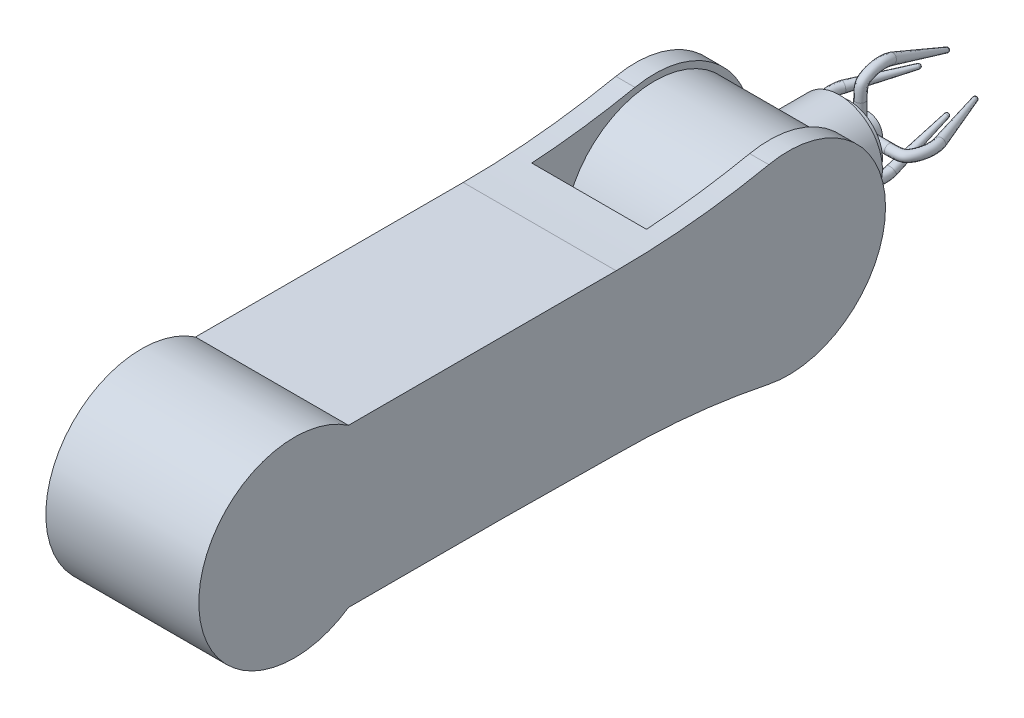
SolidWorks part; units mm, degrees
ref_plane "Front Plane" through (0, 0, 0) normal (0, 0, 1) x (1, 0, 0)
ref_plane "Top Plane" through (0, 0, 0) normal (0, 1, 0) x (1, 0, 0)
ref_plane "Right Plane" through (0, 0, 0) normal (1, 0, 0) x (0, 0, -1)
sketch "Sketch1" plane through (0, 0, 0) normal (1, 0, 0) x (0, 0, -1)
  circle A0 centre (0, 0) radius 50
  dimension "D1" = 100
extrude "Boss-Extrude1" add sketch "Sketch1" along normal mid plane 80
sketch "Sketch2" plane through (40, 0, 0) normal (1, 0, 0) x (0, 0, -1)
  line L0 (28.2566, 41.25) -> (28.2566, -41.25)
  line L1 (28.2566, -41.25) -> (108.2566, -41.25)
  line L2 (108.2566, -41.25) -> (108.2566, 41.25)
  line L3 (108.2566, 41.25) -> (28.2566, 41.25)
  circle A0 centre (0, 0) radius 50 construction
  dimension "D1" = 82.5
  dimension "D2" = 80
extrude "Boss-Extrude2" add sketch "Sketch2" against normal blind 80
ref_axis "Axis1" through (134.8481, 0, 0) along (-1, 0, 0)
sketch "Sketch5" plane through (0, 0, 0) normal (1, 0, 0) x (0, 0, -1)
  line L0 (108.2566, 41.25) -> (168.2566, 41.25)
  line L1 (168.2566, -41.9043) -> (108.2566, -41.25)
  line L2 (108.2566, -41.25) -> (108.2566, 41.25)
  line L3 (258.335, -0.3271) -> (393.5129, -0.3271) construction
  arc A0 (168.2566, 41.25) -> (248.0774, 49.3973) centre (168.2566, 436.3342) ccw
  arc A1 (248.0774, 49.3973) -> (248.0774, -50.0516) centre (258.335, -0.3271) cw
  arc A2 (248.0774, -50.0516) -> (168.2566, -41.9043) centre (168.2566, -436.9884) ccw
  dimension "D3" = 150.0784
  dimension "D1" = 60
  dimension "D2" = 60
extrude "Boss-Extrude4" add sketch "Sketch5" against normal mid plane 80
sketch "Sketch6" plane through (0, 0, 0) normal (0, 1, 0) x (1, 0, 0)
  line L0 (30, 260.643) -> (30, 309.1065)
  line L2 (40, 309.1065) -> (-40, 309.1065) construction
  line L3 (30, 309.1065) -> (-30, 309.1065)
  line L4 (-30, 309.1065) -> (-30, 260.643)
  line L6 (40, 168.2566) -> (40, 248.0774) construction
  line L7 (-40, 248.0774) -> (-40, 168.2566) construction
  line L9 (-30, 260.643) -> (-30, 217.1791)
  line L11 (30, 217.1791) -> (30, 260.643)
  line L12 (-30, 217.1791) -> (-30, 194.1065)
  line L13 (-30, 194.1065) -> (30, 194.1065)
  line L14 (30, 194.1065) -> (30, 217.1791)
  point P6 (0, 194.1065)
  dimension "D1" = 10
  dimension "D2" = 10
  dimension "D3" = 115
extrude "Cut-Extrude1" cut sketch "Sketch6" against normal mid plane 120
sketch "Sketch9" plane through (30, 0, 0) normal (-1, 0, 0) x (0, 0, 1)
  circle A0 centre (-258.335, -0.3271) radius 47.5
  dimension "D1" = 95
extrude "Boss-Extrude5" add sketch "Sketch9" along normal blind 60
ref_plane "Plane1" through (0, 0, -260) normal (0, 0, 1) x (1, 0, 0)
sketch "Sketch10" plane through (0, 0, -260) normal (0, 0, 1) x (1, 0, 0)
  circle A0 centre (0, 0) radius 22.5
  circle A1 centre (0, 0) radius 17.5
  dimension "D1" = 45
  dimension "D2" = 35
extrude "Boss-Extrude6" add sketch "Sketch10" against normal blind 65
sketch "Sketch11" plane through (0, 0, -325) normal (0, 0, -1) x (-1, 0, 0)
  circle A0 centre (0, 0) radius 17.5 construction
  circle A1 centre (0, 0) radius 17.5
extrude "Boss-Extrude7" add sketch "Sketch11" along normal blind 5 separate body
sketch "Sketch12" plane through (0, 0, -330) normal (0, 0, -1) x (-1, 0, 0)
  circle A0 centre (0, 0) radius 7.5
  dimension "D1" = 15
extrude "Boss-Extrude8" add sketch "Sketch12" along normal blind 10
sketch "Sketch14" plane through (0, 0, 0) normal (0, 1, 0) x (1, 0, 0)
  line L0 (7.5, 340) -> (-7.5, 340) construction
  circle A0 centre (0, 336) radius 2.5
  dimension "D1" = 5
  dimension "D2" = 4
extrude "Boss-Extrude10" add sketch "Sketch14" along normal blind 15
sketch "Sketch15" plane through (0, 0, 0) normal (1, 0, 0) x (0, 0, -1)
  line L0 (338.5, 15) -> (333.5, 15) construction
  spline S0 degree 3 poles (336, 15) (335.9837, 16.3681) (336.0349, 20.0109) (337.7029, 24.6293) (346.6057, 27.2197) (352.142, 25.2915) knots 0 0 0 0 0.320344 0.420344 1 1 1 1
sketch "Sketch16" plane through (0, 15, 0) normal (0, 1, 0) x (1, 0, 0)
  circle A1 centre (0, 336) radius 2.5
  circle A2 centre (0, 336) radius 2.5
  dimension "D1" = 0
sweep "Sweep1" add profiles "Sketch16" path "Sketch15"
sketch "Sketch18" plane through (0, 0, 0) normal (1, 0, 0) x (0, 0, -1)
  line L0 (352.142, 25.2915) -> (382.13, 14.4449) construction
  line L1 (351.2916, 22.9406) -> (352.9923, 27.6425) construction
  line L2 (352.142, 25.2915) -> (351.2916, 22.9406)
  line L3 (352.142, 25.2915) -> (382.13, 14.4449)
  line L4 (351.2916, 22.9406) -> (380.6103, 13.7958)
  arc A0 (382.13, 14.4449) -> (380.6103, 13.7958) centre (381.0456, 14.8801) cw
  dimension "D1" = 90
revolve "Revolve1" add sketch "Sketch18" angle 360 about L0
pattern_circular "CirPattern1" count 4 over 360 about axis through (0, 0, -340) along (0, 0, -1) of "Boss-Extrude10", "Sweep1", "Revolve1"
